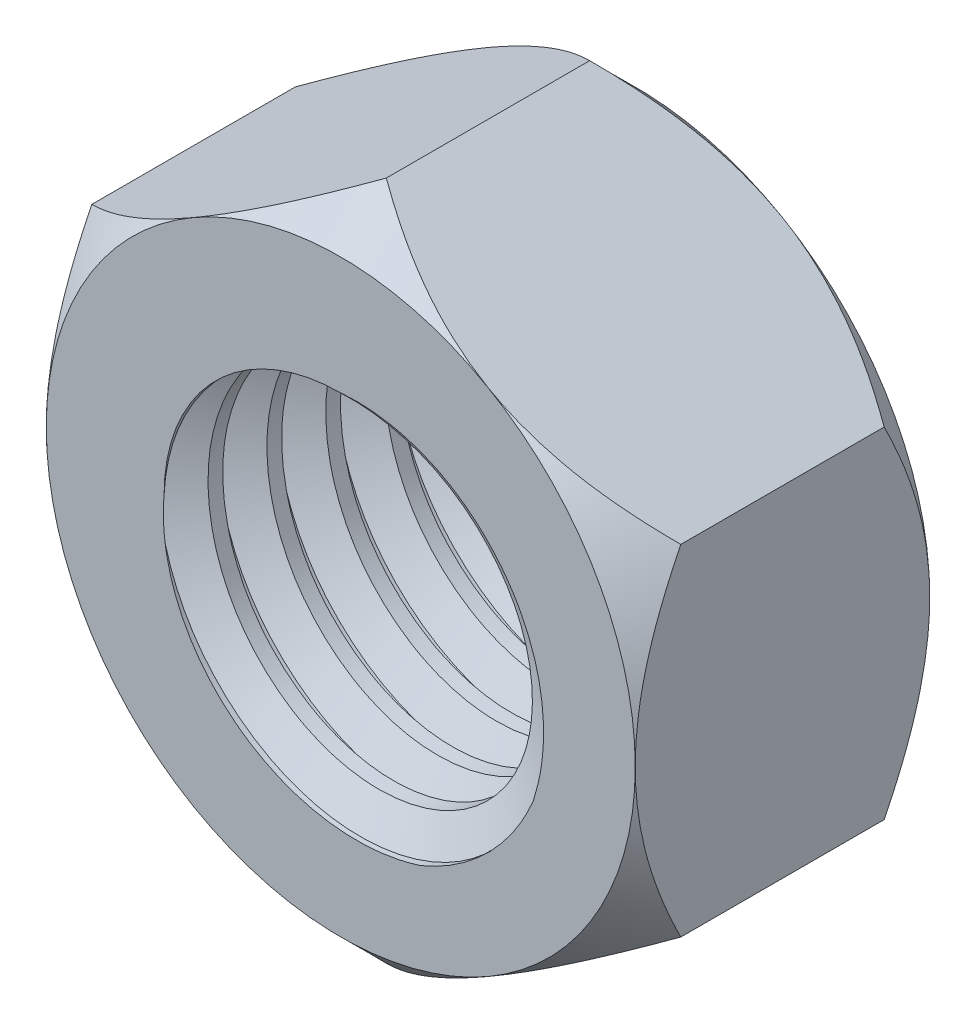
SolidWorks part; units mm, degrees
ref_plane "Front Plane" through (0, 0, 0) normal (0, 0, 1) x (1, 0, 0)
ref_plane "Top Plane" through (0, 0, 0) normal (0, 1, 0) x (1, 0, 0)
ref_plane "Right Plane" through (0, 0, 0) normal (1, 0, 0) x (0, 0, -1)
sketch "Sketch1" plane through (0, 0, 0) normal (0, 0, 1) x (1, 0, 0)
  line L1 (0, -5.7735) -> (5, -2.8868)
  line L2 (5, -2.8868) -> (5, 2.8868)
  line L3 (5, 2.8868) -> (0, 5.7735)
  line L4 (0, 5.7735) -> (-5, 2.8868)
  line L5 (-5, 2.8868) -> (-5, -2.8868)
  line L6 (-5, -2.8868) -> (0, -5.7735)
  circle A0 centre (0, 0) radius 5 construction
  circle A1 centre (0, 0) radius 3
  dimension "D1" = 10
  dimension "D2" = 6
extrude "Boss-Extrude1" add sketch "Sketch1" along normal mid plane 5 contours L5 L6 L1 L2 L3 L4 A1 | A1 region at (-2.4236, -4.1978, 0) region at (0, 0, 0)
sketch "Sketch2" plane through (0, 0, 2.5) normal (0, 0, 1) x (1, 0, 0)
  circle A0 centre (0, 0) radius 3
  dimension "D1" = 6
sketch "Sketch3" plane through (0, 0, 2.5) normal (0, 0, 1) x (1, 0, 0)
  circle A0 centre (0, 0) radius 5
  dimension "D1" = 10
extrude "Cut-Extrude1" cut sketch "Sketch3" against normal blind 27.5 draft 45 flip side to cut
mirror "Mirror1" about plane through (0, 0, 0) normal (0, 0, 1) of "Cut-Extrude1"
extrude "Cut-Extrude2" cut sketch "Sketch2" against normal blind 27.5
thread "Thread2" pitch 1 method cut trim with start face yes trim with end face yes profile "Thread Profile2" start angle 0, offset 2, length 0, pitch 1, diameter 6
ref_plane "Plane2" through (-3, 0, 4.5) normal (0, -1, 0) x (-1, 0, 0)
sketch "Thread Profile2" plane through (-3, 0, 4.5) normal (0, -1, 0) x (-1, 0, 0)
  line L0 (0, 0) -> (0, 1) construction
  line L1 (0, 0) -> (0.5413, 0.3125)
  line L2 (0.5413, 0.3125) -> (0.5413, 0.4375)
  line L3 (0.5413, 0.4375) -> (0, 0.75)
  line L4 (0.5413, 0.375) -> (0, 0.375) construction
  line L11 (0, 0) -> (0, 0.75)
  point P2 (0, 0)
  dimension "Pitch" = 1
  dimension "Profile_Angle" = 60
  dimension "Profile_Land" = 0.125
  dimension "Profile_Height" = 0.5413
